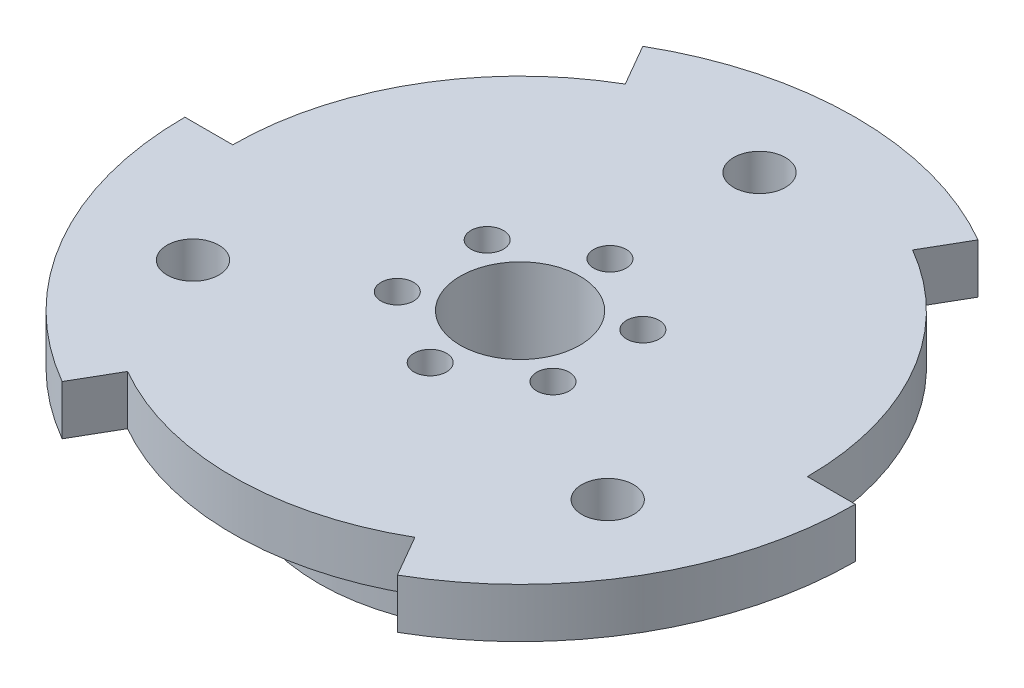
SolidWorks part; units mm, degrees
ref_plane "Front Plane" through (0, 0, 0) normal (0, 0, 1) x (1, 0, 0)
ref_plane "Top Plane" through (0, 0, 0) normal (0, 1, 0) x (1, 0, 0)
ref_plane "Right Plane" through (0, 0, 0) normal (1, 0, 0) x (0, 0, -1)
sketch "Sketch7" plane through (0, 0, 0) normal (0, 1, 0) x (1, 0, 0)
  line L1 (-11.3137, -11.3137) -> (11.3137, -11.3137)
  line L2 (-11.3137, -11.3137) -> (-11.3137, 11.3137)
  line L3 (-11.3137, 11.3137) -> (11.3137, 11.3137)
  line L4 (11.3137, -11.3137) -> (11.3137, 11.3137)
  line L5 (-11.3137, -11.3137) -> (11.3137, 11.3137) construction
  line L6 (-11.3137, 11.3137) -> (11.3137, -11.3137) construction
  circle A0 centre (0, 0) radius 16.1
  point P0 (0, 0)
  dimension "D1" = 32
extrude "Boss-Extrude2" add sketch "Sketch7" along normal blind 8.2 contours L1 L4 L3 L2 | A0 L4 L1 L2 L3 region at (0, 0, 0) region at (-15.6446, 0, 0)
sketch "Sketch1" plane through (0, 8.2, 0) normal (0, 1, 0) x (1, 0, 0)
  line L0 (0, 0) -> (0, 35.4208) construction
  line L1 (-20, -20) -> (20, -20)
  line L2 (-20, -20) -> (-20, 20)
  line L3 (-20, 20) -> (20, 20)
  line L4 (20, -20) -> (20, 20)
  line L5 (-20, -20) -> (20, 20) construction
  line L6 (-20, 20) -> (20, -20) construction
  line L7 (17.5, 30.3109) -> (15, 25.9808)
  line L8 (-17.5, 30.3109) -> (-15, 25.9808)
  line L9 (17.5, -30.3109) -> (15, -25.9808)
  line L10 (35, 0) -> (30, 0)
  line L11 (-35, 0) -> (-30, 0)
  line L12 (-17.5, -30.3109) -> (-15, -25.9808)
  circle A0 centre (0, 0) radius 6.25
  circle A1 centre (0, 25) radius 2.7073
  circle A2 centre (21.6506, -12.5) radius 2.7073
  circle A3 centre (-21.6506, -12.5) radius 2.7073
  circle A4 centre (0, 0) radius 30
  arc A5 (17.5, 30.3109) -> (-17.5, 30.3109) centre (0, 0) ccw
  arc A6 (17.5, -30.3109) -> (35, 0) centre (0, 0) ccw
  arc A7 (-35, 0) -> (-17.5, -30.3109) centre (0, 0) ccw
  point P0 (0, 0)
  point P18 (0, 0)
  point P21 (0, 35)
  point P34 (0, 0)
  dimension "D2" = 12.5
  dimension "D6" = 60
  dimension "D7" = 5
  dimension "D8" = 35
  dimension "D9" = 3
  dimension "D1" = 25
  dimension "D3" = 40
  dimension "D4" = 40
  dimension "D5" = 3
extrude "Boss-Extrude1" add sketch "Sketch1" along normal blind 5.18 contours L11 A7 L12 A4 | L9 A6 L10 A4 | L7 A5 L8 A4 | L2 A3 | L4 A2 | A1 | L2 A3 | L4 A2 | A0 | A4 region at (-21.9823, 8.2, 12.5) region at (-19.5694, 8.2, 12.5) region at (19.5694, 8.2, 12.5) region at (21.9823, 8.2, 12.5) region at (0, 8.2, -31.0964) region at (26.9303, 8.2, 15.5482) region at (-26.9303, 8.2, 15.5482) region at (0, 8.2, 0) region at (0, 8.2, -25)
sketch "Sketch5" [suppressed] plane through (0, 0, 0) normal (1, 0, 0) x (0, 0, -1)
  line L0 (-10.331, 15) -> (10.331, 0) construction
  line L1 (10, 5) -> (-10, 5)
  line L2 (10, 5) -> (10, 10)
  line L3 (10, 10) -> (-10, 10)
  line L4 (-10, 5) -> (-10, 10)
  line L5 (10, 5) -> (-10, 10) construction
  line L6 (10, 10) -> (-10, 5) construction
  line L7 (20, 7.5) -> (-20, 7.5) construction
  line L8 (20, 15) -> (20, 0) construction
  line L9 (-20, 15) -> (-20, 0) construction
  line L10 (-10.3541, 15) -> (-10.3078, 15) construction
  line L11 (-10.3541, 0) -> (20, 0) construction
  point P0 (0, 7.5)
  dimension "D1" = 20
  dimension "D2" = 5
sketch "Sketch3" [suppressed] plane through (0, 0, -20) normal (0, 0, -1) x (-1, 0, 0)
  line L3 (15.1539, 15) -> (15.1539, 3) construction
  line L4 (20, 15) -> (10.3078, 15) construction
  circle A0 centre (15.1539, 3) radius 1.6
  dimension "D2" = 3.2
  dimension "D1" = 12
sketch "Sketch2" [suppressed] plane through (0, 0, 20) normal (0, 0, 1) x (1, 0, 0)
  line L0 (0, 27.8717) -> (0, -11.9207) construction
  line L1 (20, 2) -> (10, 2)
  line L3 (10, 2) -> (10, 0)
  line L4 (-20, 0) -> (20, 0) construction
  line L5 (20, 15) -> (20, 0) construction
  circle A0 centre (10, 2) radius 1.6
  circle A1 centre (-10, 2) radius 1.6
  dimension "D3" = 3.2
  dimension "D1" = 10
  dimension "D2" = 2
sketch "Sketch6" plane through (0, 13.38, 0) normal (0, 1, 0) x (1, 0, 0)
  circle A9 centre (0, -9.385) radius 1.7
  circle A10 centre (-8.1276, -4.6925) radius 1.7
  circle A11 centre (-8.1276, 4.6925) radius 1.7
  circle A12 centre (0, 9.385) radius 1.7
  circle A13 centre (8.1276, 4.6925) radius 1.7
  circle A14 centre (8.1276, -4.6925) radius 1.7
  point P16 (0, 0)
  dimension "D2" = 9.385
  dimension "D1" = 3.4
  dimension "D3" = 9.385
extrude "Cut-Extrude1" cut sketch "Sketch6" along normal through all and the other way through all
fillet "Fillet2" [suppressed] radius 5
sketch "Sketch9" plane through (0, 13.38, 0) normal (0, 1, 0) x (1, 0, 0)
  line L6 (-30, 0) -> (-35, 0)
  line L7 (-17.5, -30.3109) -> (-15, -25.9808)
  line L8 (15, -25.9808) -> (17.5, -30.3109)
  line L9 (35, 0) -> (30, 0)
  line L10 (15, 25.9808) -> (17.5, 30.3109)
  line L11 (-17.5, 30.3109) -> (-15, 25.9808)
  line L12 (-30, 0) -> (-35, 0)
  line L13 (-17.5, -30.3109) -> (-15, -25.9808)
  line L14 (15, -25.9808) -> (17.5, -30.3109)
  line L15 (35, 0) -> (30, 0)
  line L16 (15, 25.9808) -> (17.5, 30.3109)
  line L17 (-17.5, 30.3109) -> (-15, 25.9808)
  arc A6 (-35, 0) -> (-17.5, -30.3109) centre (0, 0) ccw
  arc A7 (-15, -25.9808) -> (15, -25.9808) centre (0, 0) ccw
  arc A8 (17.5, -30.3109) -> (35, 0) centre (0, 0) ccw
  arc A9 (30, 0) -> (15, 25.9808) centre (0, 0) ccw
  arc A10 (17.5, 30.3109) -> (-17.5, 30.3109) centre (0, 0) ccw
  arc A11 (-15, 25.9808) -> (-30, 0) centre (0, 0) ccw
  arc A12 (-35, 0) -> (-17.5, -30.3109) centre (0, 0) ccw
  arc A13 (-15, -25.9808) -> (15, -25.9808) centre (0, 0) ccw
  arc A14 (17.5, -30.3109) -> (35, 0) centre (0, 0) ccw
  arc A15 (30, 0) -> (15, 25.9808) centre (0, 0) ccw
  arc A16 (17.5, 30.3109) -> (-17.5, 30.3109) centre (0, 0) ccw
  arc A17 (-15, 25.9808) -> (-30, 0) centre (0, 0) ccw
  circle M14 centre (8.1276, -4.6925) radius 1.7
  circle M15 centre (8.1276, 4.6925) radius 1.7
  circle M16 centre (0, 9.385) radius 1.7
  circle M17 centre (-8.1276, 4.6925) radius 1.7
  circle M18 centre (-8.1276, -4.6925) radius 1.7
  circle M31 centre (21.6506, -12.5) radius 2.7073
  circle M32 centre (0, 25) radius 2.7073
  circle M33 centre (-21.6506, -12.5) radius 2.7073
  circle M34 centre (0, 0) radius 6.25
  dimension "D1" = 0
extrude "Cut-Extrude2" cut sketch "Sketch9" against normal through all contours M33 | M34 | M31 | M32 | M14 | M15 | M16 | M17 | M18 region at (8.1276, 13.38, 4.6925) region at (8.1276, 13.38, -4.6925) region at (0, 13.38, -9.385) region at (-8.1276, 13.38, -4.6925) region at (-8.1276, 13.38, 4.6925) region at (21.6506, 13.38, 12.5) region at (0, 13.38, -25) region at (-21.6506, 13.38, 12.5) region at (0, 13.38, 0)
sketch "Sketch10" plane through (0, 8.2, 0) normal (0, -1, 0) x (1, 0, 0)
  circle A1 centre (0, 0) radius 16.1 construction
  circle A3 centre (0, 0) radius 21
  point P0 (0, 0)
  circle M2 centre (0, 0) radius 16.1
  dimension "D1" = 42
extrude "Boss-Extrude3" add sketch "Sketch10" along normal blind 9 contours A3 M2 region at (-20.406, 8.2, 0)
chamfer "Chamfer1" distance 1.5 angle 45 1 edges at (0, -0.8, -16.1)
